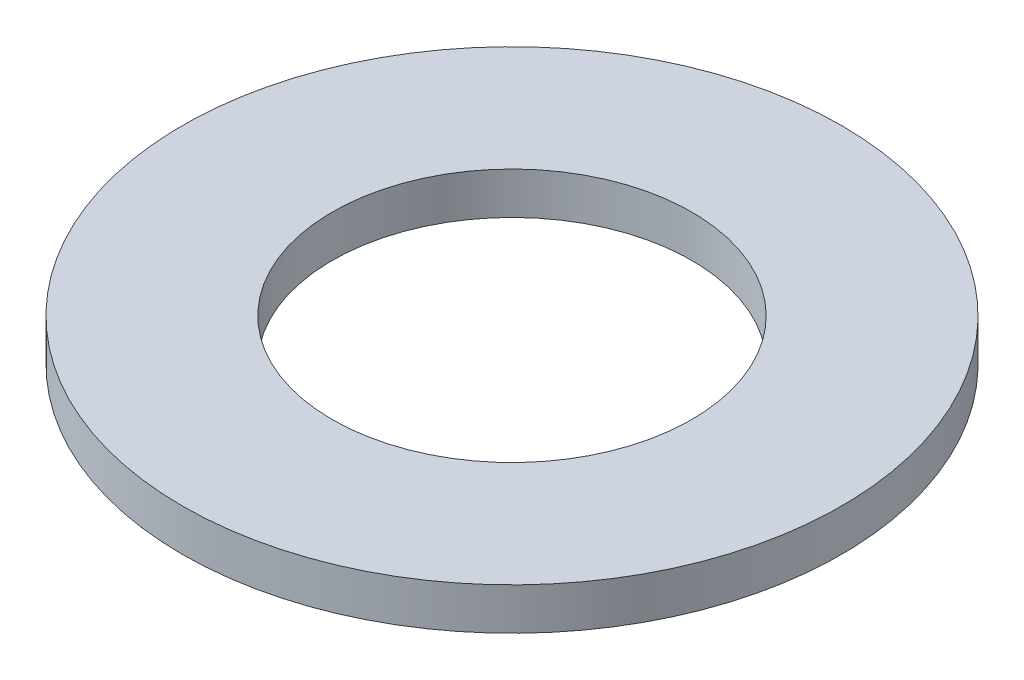
SolidWorks part; units mm, degrees
ref_plane "Front Plane" through (0, 0, 0) normal (0, 0, 1) x (1, 0, 0)
ref_plane "Top Plane" through (0, 0, 0) normal (0, 1, 0) x (1, 0, 0)
ref_plane "Right Plane" through (0, 0, 0) normal (1, 0, 0) x (0, 0, -1)
sketch "Sketch1" plane through (0, 0, 0) normal (0, 1, 0) x (1, 0, 0)
  circle A0 centre (0, 0) radius 55
  dimension "FLANGE_OD" = 110
extrude "Boss-Extrude1" add sketch "Sketch1" along normal blind 7
sketch "Sketch2" plane through (0, 0, 0) normal (0, 1, 0) x (1, 0, 0)
  circle A0 centre (0, 0) radius 30
  dimension "BORE_D" = 60
extrude "Cut-Extrude1" cut sketch "Sketch2" along normal through all
sketch "Sketch3" plane through (0, 7, 0) normal (0, 1, 0) x (1, 0, 0)
  circle A0 centre (0, 0) radius 23.1171 construction
  circle A1 centre (-23.1171, 0) radius 1.6054
  dimension "BOLT_D" = 3.2107
  dimension "BOLT_PCD" = 46.2343
extrude "Cut-Extrude2" cut sketch "Sketch3" against normal blind 5.4586 rebuild error yes
pattern_circular "CirPattern1" count 6 over 360 rebuild error yes
